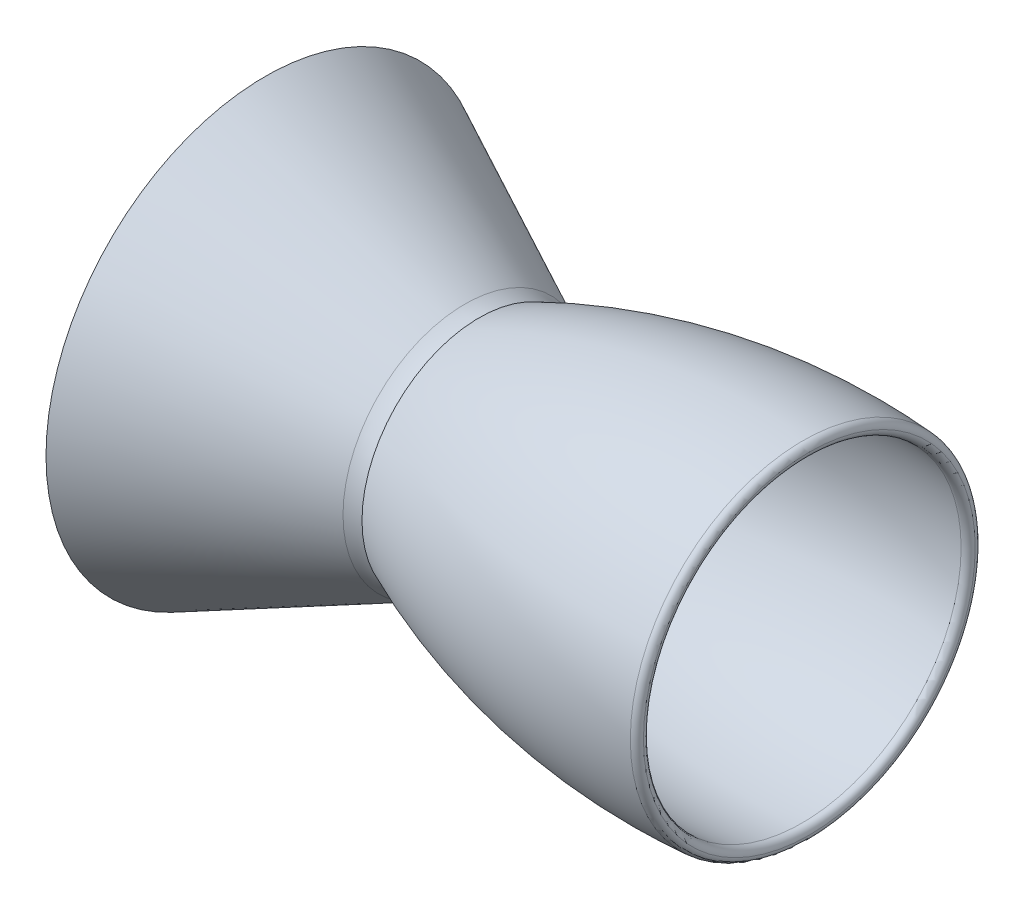
SolidWorks part; units mm, degrees
ref_plane "Front Plane" through (0, 0, 0) normal (0, 0, 1) x (1, 0, 0)
ref_plane "Top Plane" through (0, 0, 0) normal (0, 1, 0) x (1, 0, 0)
ref_plane "Right Plane" through (0, 0, 0) normal (1, 0, 0) x (0, 0, -1)
sketch "Sketch1" plane through (0, 0, 0) normal (0, 0, 1) x (1, 0, 0)
  line L0 (-150.5272, 0) -> (150.5272, 0) construction
  line L1 (-1000, 750) -> (-287.9674, 402.9473)
  line L3 (-1000, 805.6231) -> (-266.0605, 447.8927)
  line L7 (-978.0931, 794.9454) -> (-266.0605, 447.8927) construction
  line L8 (-213.438, 430.7615) -> (1068.696, 717.6726) construction
  line L9 (-1000, 805.6231) -> (-1000, 750)
  line L10 (1000, 632.9023) -> (1000, 582.745)
  line L11 (-211.7453, 379.9037) -> (1079.6147, 668.8793) construction
  arc A0 (-287.9674, 402.9473) -> (-206.4681, 379.2512) centre (-178.4329, 627.6743) ccw
  arc A1 (-266.0605, 447.8927) -> (-213.438, 430.7615) centre (-178.4329, 627.6743) ccw
  arc A2 (-213.438, 430.7615) -> (1000, 632.9023) centre (800.1154, -1910.3682) cw
  arc A3 (-206.4681, 379.2512) -> (1000, 582.745) centre (800.1154, -1910.3682) cw
  arc A4 (-193.573, 384.877) -> (996.0824, 583.056) centre (800.1154, -1910.3682) cw construction
  arc A5 (-287.9674, 402.9473) -> (-211.7453, 379.9037) centre (-178.4329, 627.6743) ccw construction
  point P4 (0, 0)
  point P10 (0, 0)
  point P19 (-57, 0)
  point P26 (0, 0)
  point P28 (-250.7364, 252.4487)
  dimension "D2" = 250
  dimension "D9" = 50
  dimension "D5" = 2000
  dimension "D6" = 750
  dimension "D7" = 50
  dimension "D8" = 1000
revolve "Revolve1" add sketch "Sketch1" angle 360 about L0
fillet "Fillet1" radius 25 2 edges at (1000, 0, 632.9023) (1000, 0, 582.745)
